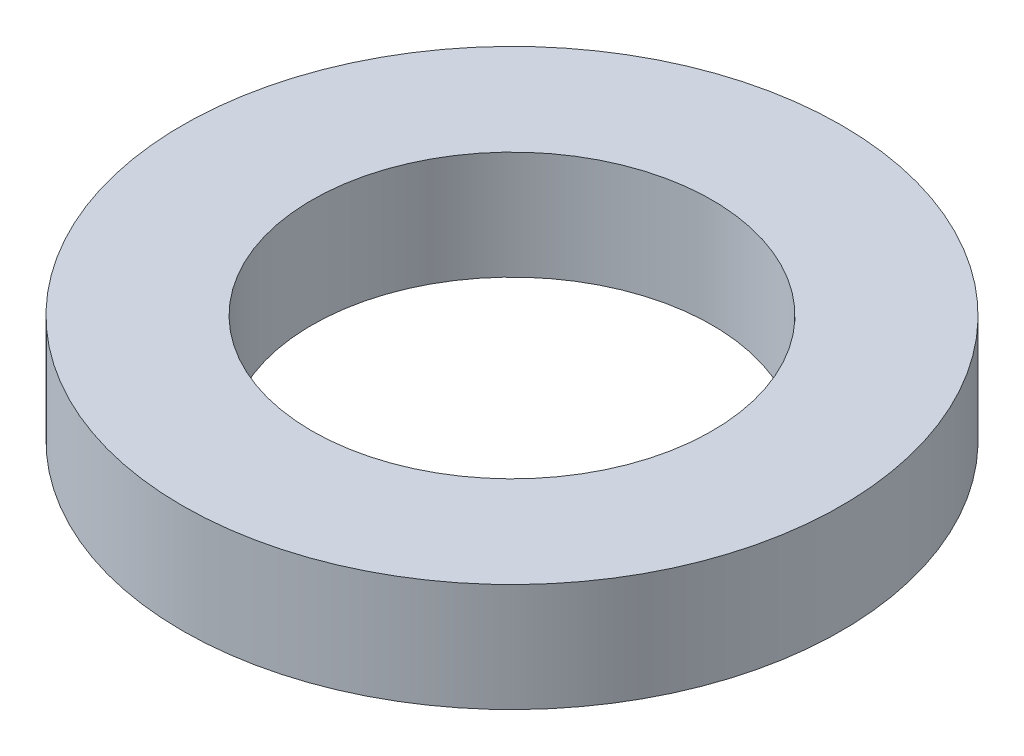
SolidWorks part; units mm, degrees
ref_plane "Front Plane" through (0, 0, 0) normal (0, 0, 1) x (1, 0, 0)
ref_plane "Top Plane" through (0, 0, 0) normal (0, 1, 0) x (1, 0, 0)
ref_plane "Right Plane" through (0, 0, 0) normal (1, 0, 0) x (0, 0, -1)
sketch "Sketch1" plane through (0, 0, 0) normal (0, 1, 0) x (1, 0, 0)
  circle A0 centre (0, 0) radius 70
  dimension "FLANGE_OD" = 140
extrude "Boss-Extrude1" add sketch "Sketch1" along normal blind 23
sketch "Sketch2" plane through (0, 0, 0) normal (0, 1, 0) x (1, 0, 0)
  circle A0 centre (0, 0) radius 42.5
  dimension "BORE_D" = 85
extrude "Cut-Extrude1" cut sketch "Sketch2" along normal through all
sketch "Sketch3" plane through (0, 23, 0) normal (0, 1, 0) x (1, 0, 0)
  circle A0 centre (0, 0) radius 31.3455 construction
  circle A1 centre (-31.3455, 0) radius 2.7034
  dimension "BOLT_D" = 5.4068
  dimension "BOLT_PCD" = 62.691
extrude "Cut-Extrude2" cut sketch "Sketch3" against normal blind 15.1823 rebuild error yes
pattern_circular "CirPattern1" count 4 over 360 rebuild error yes
